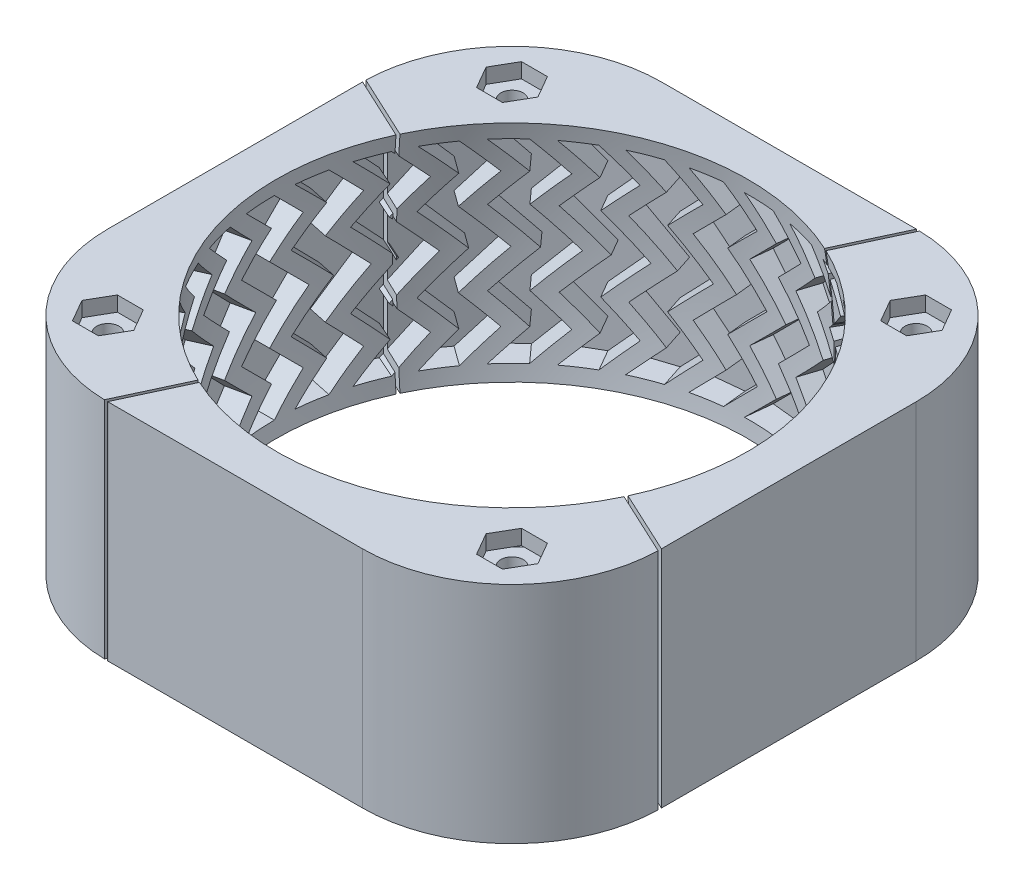
SolidWorks part; units mm, degrees
material "ABS"
ref_plane "Спереди" through (0, 0, 0) normal (0, 0, 1) x (1, 0, 0)
ref_plane "Сверху" through (0, 0, 0) normal (0, 1, 0) x (1, 0, 0)
ref_plane "Справа" through (0, 0, 0) normal (1, 0, 0) x (0, 0, -1)
sketch "Эскиз2" plane through (0, 0, 0) normal (0, 1, 0) x (1, 0, 0)
  line L1 (37, -37) -> (-37, -37)
  line L2 (37, -37) -> (37, 37)
  line L3 (37, 37) -> (-37, 37)
  line L4 (-37, -37) -> (-37, 37)
  line L5 (37, -37) -> (-37, 37) construction
  line L6 (37, 37) -> (-37, -37) construction
  point P0 (0, 0)
  dimension "D1" = 74
  dimension "D2" = 74
extrude "Бобышка-Вытянуть1" add sketch "Эскиз2" along normal blind 30
sketch "Эскиз3" plane through (0, 0, 0) normal (1, 0, 0) x (0, 0, -1)
  line L0 (0, 41.3522) -> (0, -3.1956) construction
  line L1 (-34.4708, 15) -> (34.6551, 15) construction
  line L3 (-31.5, 30) -> (-31.5, 0)
  line L5 (0, 0) -> (0, 30)
  line L7 (-37, 30) -> (37, 30) construction
  line L9 (-31.5, 30) -> (0, 30)
  line L12 (-31.5, 0) -> (0, 0)
  line L13 (-40.4768, 0) -> (40.1693, 0) construction
  line L14 (-37, 0) -> (37, 0) construction
  arc A0 (-31.5, 0) -> (-31.5, 30) centre (80.5, 15) cw
  point P7 (-32.5, 15)
  dimension "D1" = 1
  dimension "D2" = 63
revolve "Вырез-Повернуть1" cut sketch "Эскиз3" angle 360 about L0 region at (0, 15, 15.75) region at (0, 15, 31.9002)
fillet "Скругление1" radius 20 4 edges at (-37, 15, 37) (-37, 15, -37) (37, 15, -37) (37, 15, 37)
ref_plane "Плоскость5" through (31, 0, 0) normal (1, 0, 0) x (0, 0, -1)
sketch "Эскиз7" plane through (31, 0, 0) normal (1, 0, 0) x (0, 0, -1)
  line L0 (0, 44.0212) -> (0, -3.9515) construction
  line L2 (-28.1298, 15) -> (25.9038, 15) construction
  line L3 (-17, 30) -> (17, 30) construction
  line L28 (-17, 0) -> (17, 0) construction
  line L30 (-1, 15) -> (4, 20)
  line L31 (4, 20) -> (0, 24)
  line L32 (0, 24) -> (4, 28)
  line L33 (-1, 15) -> (4, 10)
  line L34 (4, 10) -> (0, 6)
  line L35 (0, 6) -> (4, 2)
  line L36 (-5, 15) -> (0, 20)
  line L37 (0, 20) -> (-4, 24)
  line L38 (-4, 24) -> (0, 28)
  line L39 (-5, 15) -> (0, 10)
  line L40 (0, 10) -> (-4, 6)
  line L41 (-4, 6) -> (0, 2)
  line L42 (0, 28) -> (4, 28)
  line L43 (0, 2) -> (4, 2)
  point P12 (-1, 15)
  point P22 (-5, 15)
  dimension "D1" = 2
  dimension "D2" = 4
  dimension "D4" = 2
extrude "Вырез-Вытянуть3" cut sketch "Эскиз7" along normal blind 4 contours L33 | L43 L35 L34 L33 L30 L31 L32 L42 L38 L37 L36 L39 L40 L41
pattern_circular "Круговой массив1" count 30 over 360 about axis through (0, 30, 0) along (0, 1, 0) of "Вырез-Вытянуть3"
sketch "Эскиз17" plane through (0, 0, 0) normal (0, 1, 0) x (1, 0, 0)
  line L1 (27, -27) -> (-27, -27)
  line L2 (27, -27) -> (27, 27)
  line L3 (27, 27) -> (-27, 27)
  line L4 (-27, -27) -> (-27, 27)
  line L5 (27, -27) -> (-27, 27) construction
  line L6 (27, 27) -> (-27, -27) construction
  circle A0 centre (-27, 27) radius 1.5
  circle A1 centre (27, 27) radius 1.5
  circle A2 centre (27, -27) radius 1.5
  circle A3 centre (-27, -27) radius 1.5
  point P0 (0, 0)
  dimension "D3" = 3
  dimension "D1" = 54
  dimension "D2" = 54
extrude "Вырез-Вытянуть12" cut sketch "Эскиз17" along normal through all contours A3 | A2 | A1 | A0
sketch "Эскиз18" plane through (0, 30, 0) normal (0, 1, 0) x (1, 0, 0)
  line L1 (-28.7321, 30) -> (-30.4641, 27)
  line L2 (-30.4641, 27) -> (-28.7321, 24)
  line L3 (-28.7321, 24) -> (-25.2679, 24)
  line L4 (-25.2679, 24) -> (-23.5359, 27)
  line L5 (-23.5359, 27) -> (-25.2679, 30)
  line L6 (-25.2679, 30) -> (-28.7321, 30)
  line L7 (25.2679, 30) -> (23.5359, 27)
  line L8 (23.5359, 27) -> (25.2679, 24)
  line L9 (25.2679, 24) -> (28.7321, 24)
  line L10 (28.7321, 24) -> (30.4641, 27)
  line L11 (30.4641, 27) -> (28.7321, 30)
  line L12 (28.7321, 30) -> (25.2679, 30)
  line L13 (25.2679, -24) -> (23.5359, -27)
  line L14 (23.5359, -27) -> (25.2679, -30)
  line L15 (25.2679, -30) -> (28.7321, -30)
  line L16 (28.7321, -30) -> (30.4641, -27)
  line L17 (30.4641, -27) -> (28.7321, -24)
  line L18 (28.7321, -24) -> (25.2679, -24)
  line L19 (-28.7321, -24) -> (-30.4641, -27)
  line L20 (-30.4641, -27) -> (-28.7321, -30)
  line L21 (-28.7321, -30) -> (-25.2679, -30)
  line L22 (-25.2679, -30) -> (-23.5359, -27)
  line L23 (-23.5359, -27) -> (-25.2679, -24)
  line L24 (-25.2679, -24) -> (-28.7321, -24)
  circle A0 centre (-27, 27) radius 3 construction
  circle A1 centre (27, 27) radius 3 construction
  circle A2 centre (27, -27) radius 3 construction
  circle A3 centre (-27, -27) radius 3 construction
  dimension "D1" = 6
extrude "Вырез-Вытянуть13" cut sketch "Эскиз18" against normal blind 2
sketch "Эскиз19" plane through (0, 0, 0) normal (0, 1, 0) x (1, 0, 0)
  line L1 (-28.7321, -30) -> (-25.2679, -30)
  line L2 (-25.2679, -30) -> (-23.5359, -27)
  line L3 (-23.5359, -27) -> (-25.2679, -24)
  line L4 (-25.2679, -24) -> (-28.7321, -24)
  line L5 (-28.7321, -24) -> (-30.4641, -27)
  line L6 (-30.4641, -27) -> (-28.7321, -30)
  line L7 (25.2679, -30) -> (28.7321, -30)
  line L8 (28.7321, -30) -> (30.4641, -27)
  line L9 (30.4641, -27) -> (28.7321, -24)
  line L10 (28.7321, -24) -> (25.2679, -24)
  line L11 (25.2679, -24) -> (23.5359, -27)
  line L12 (23.5359, -27) -> (25.2679, -30)
  line L13 (25.2679, 24) -> (28.7321, 24)
  line L14 (28.7321, 24) -> (30.4641, 27)
  line L15 (30.4641, 27) -> (28.7321, 30)
  line L16 (28.7321, 30) -> (25.2679, 30)
  line L17 (25.2679, 30) -> (23.5359, 27)
  line L18 (23.5359, 27) -> (25.2679, 24)
  line L19 (-28.7321, 24) -> (-25.2679, 24)
  line L20 (-25.2679, 24) -> (-23.5359, 27)
  line L21 (-23.5359, 27) -> (-25.2679, 30)
  line L22 (-25.2679, 30) -> (-28.7321, 30)
  line L23 (-28.7321, 30) -> (-30.4641, 27)
  line L24 (-30.4641, 27) -> (-28.7321, 24)
  circle A0 centre (-27, -27) radius 3 construction
  circle A1 centre (27, -27) radius 3 construction
  circle A2 centre (27, 27) radius 3 construction
  circle A3 centre (-27, 27) radius 3 construction
  dimension "D1" = 6
extrude "Вырез-Вытянуть15" cut sketch "Эскиз19" along normal blind 2
sketch "Эскиз20" plane through (0, 0, 0) normal (0, 1, 0) x (1, 0, 0)
  line L0 (17.2902, 37.079) -> (-17.2902, -37.079) construction
  line L2 (0, 52.456) -> (0, -68.5486) construction
  line L3 (-17.1089, -37.1635) -> (-17.4715, -36.9944)
  line L4 (-17.1089, -37.1635) -> (17.4715, 36.9944)
  line L5 (17.4715, 36.9944) -> (17.1089, 37.1635)
  line L6 (-17.4715, -36.9944) -> (17.1089, 37.1635)
  line L7 (-17.1089, -37.1635) -> (17.1089, 37.1635) construction
  line L8 (17.4715, 36.9944) -> (-17.4715, -36.9944) construction
  line L9 (-37.1635, 17.1089) -> (36.9944, -17.4715)
  line L10 (-37.1635, 17.1089) -> (-36.9944, 17.4715)
  line L11 (-36.9944, 17.4715) -> (37.1635, -17.1089)
  line L12 (36.9944, -17.4715) -> (37.1635, -17.1089)
  line L13 (17.1089, 37.1635) -> (-17.4715, -36.9944)
  line L14 (17.1089, 37.1635) -> (17.4715, 36.9944)
  line L15 (17.4715, 36.9944) -> (-17.1089, -37.1635)
  line L16 (-17.4715, -36.9944) -> (-17.1089, -37.1635)
  line L17 (37.1635, -17.1089) -> (-36.9944, 17.4715)
  line L18 (37.1635, -17.1089) -> (36.9944, -17.4715)
  line L19 (36.9944, -17.4715) -> (-37.1635, 17.1089)
  line L20 (-36.9944, 17.4715) -> (-37.1635, 17.1089)
  arc A0 (-37, -17) -> (-17, -37) centre (-17, -17) ccw construction
  arc A1 (37, 17) -> (17, 37) centre (17, 17) ccw construction
  point P20 (17.2902, 37.079)
  point P30 (0, 0)
  dimension "D1" = 0.4
  dimension "D2" = 4
  dimension "D3" = 25
extrude "Вырез-Вытянуть16" cut sketch "Эскиз20" along normal through all contours L4 L6 L3 | L4 L5 L6 | L6 | L4 region at (-8.6874, 0, 18.6301) region at (18.6301, 0, 8.6874) region at (-18.6301, 0, -8.6874) region at (8.6874, 0, -18.6301)
sketch "Эскиз21" plane through (0, 0, 0) normal (0, 1, 0) x (1, 0, 0)
  line L0 (-33.3959, 46.9406) -> (33.8825, 46.9406)
  line L1 (46.9406, 33.3959) -> (46.9406, -33.8825)
  line L2 (33.3959, -46.9406) -> (-33.8825, -46.9406)
  line L3 (-46.9406, -33.3959) -> (-46.9406, 33.8825)
  arc A0 (-17, 37) -> (-36.9944, 17.4715) centre (-17, 17) ccw construction
  arc A1 (37, 17) -> (17.4715, 36.9944) centre (17, 17) ccw construction
  arc A2 (17, -37) -> (36.9944, -17.4715) centre (17, -17) ccw construction
  arc A3 (-37, -17) -> (-17.4715, -36.9944) centre (-17, -17) ccw construction
  arc A4 (-17, 37) -> (-36.9944, 17.4715) centre (-17, 17) ccw
  arc A5 (37, 17) -> (17.4715, 36.9944) centre (17, 17) ccw
  arc A6 (17, -37) -> (36.9944, -17.4715) centre (17, -17) ccw
  arc A7 (-37, -17) -> (-17.4715, -36.9944) centre (-17, -17) ccw
  circle A8 centre (0.2433, 83.9326) radius 50
  circle A9 centre (83.9326, -0.2433) radius 50
  circle A10 centre (-0.2433, -83.9326) radius 50
  circle A11 centre (-83.9326, 0.2433) radius 50
  point P31 (0, 0)
  dimension "D1" = 100
  dimension "D2" = 4
extrude "Вырез-Вытянуть17" [suppressed] cut sketch "Эскиз21" along normal through all contours A8 L0 | L3 A11 | L1 A9 | L2 A10
equation "\"D2@Эскиз2\"=\"D1@Эскиз2\""
equation "\"D2@Эскиз17\"=\"D1@Эскиз17\""
